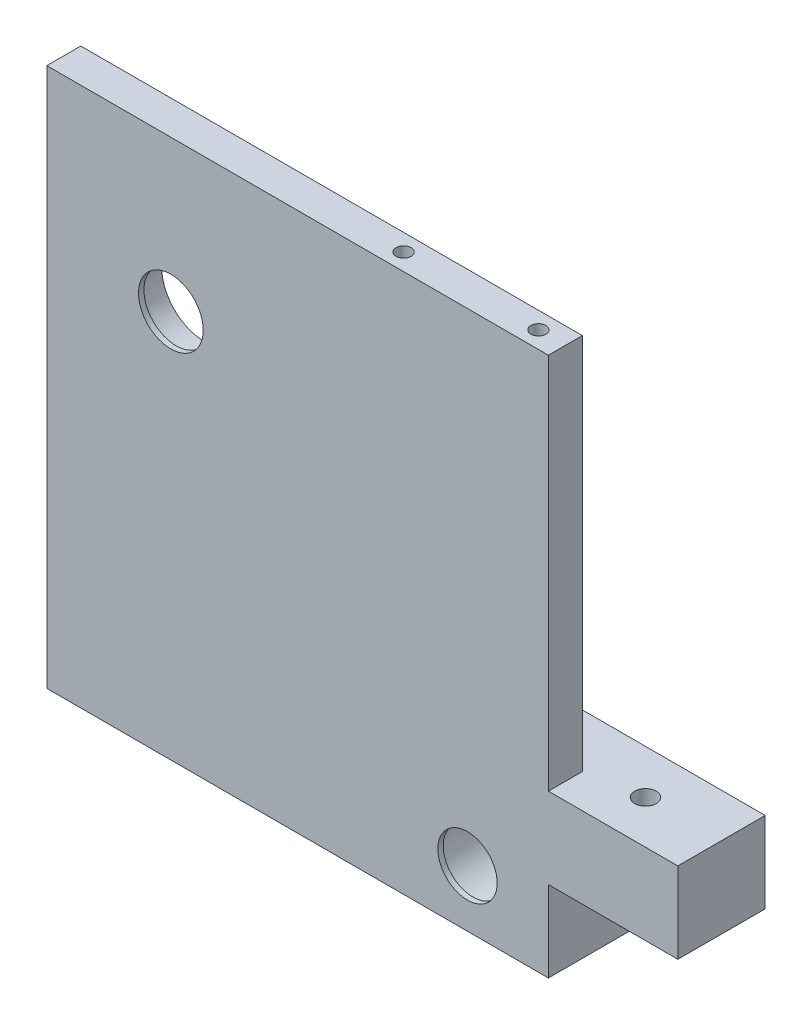
SolidWorks part; units mm, degrees
material "ABS"
ref_plane "Front Plane" through (0, 0, 0) normal (0, 0, 1) x (1, 0, 0)
ref_plane "Top Plane" through (0, 0, 0) normal (0, 1, 0) x (1, 0, 0)
ref_plane "Right Plane" through (0, 0, 0) normal (1, 0, 0) x (0, 0, -1)
sketch "Sketch1" plane through (0, 0, 0) normal (0, 0, 1) x (1, 0, 0)
  line L1 (-76.1871, 64.9281) -> (16.8129, 64.9281)
  line L2 (-76.1871, 64.9281) -> (-76.1871, -35.0719)
  line L3 (-76.1871, -35.0719) -> (16.8129, -35.0719)
  line L4 (16.8129, 64.9281) -> (16.8129, -35.0719)
  dimension "D1" = 93
  dimension "D2" = 100
extrude "Boss-Extrude2" add sketch "Sketch1" along normal blind 6.3 contours L1 L4 L3 L2
sketch "Sketch3" plane through (0, 0, 0) normal (0, 0, -1) x (-1, 0, 0)
  line L0 (76.1871, -35.0719) -> (-16.8129, -35.0719) construction
  line L1 (-16.8129, 64.9281) -> (23.1871, 64.9281)
  line L2 (-16.8129, 64.9281) -> (-16.8129, -35.0719)
  line L3 (-16.8129, -35.0719) -> (23.1871, -35.0719)
  line L4 (23.1871, 64.9281) -> (23.1871, -35.0719)
  line L5 (-16.8129, 64.9281) -> (-16.8129, -35.0719) construction
  dimension "D1" = 0
  dimension "D2" = 0
  dimension "D3" = 40
  dimension "D4" = 100
extrude "Boss-Extrude3" add sketch "Sketch3" along normal blind 9.9
sketch "Sketch4" plane through (16.8129, 0, 0) normal (1, 0, 0) x (0, 0, -1)
  line L0 (-6.3, 64.9281) -> (-6.3, -35.0719) construction
  line L1 (-6.3, -5.0719) -> (9.9, -5.0719)
  line L2 (-6.3, -5.0719) -> (-6.3, -20.0719)
  line L3 (-6.3, -20.0719) -> (9.9, -20.0719)
  line L4 (9.9, -5.0719) -> (9.9, -20.0719)
  line L5 (9.9, 64.9281) -> (9.9, -35.0719) construction
  line L6 (-6.3, -35.0719) -> (9.9, -35.0719) construction
  dimension "D1" = 15
  dimension "D2" = 15
extrude "Boss-Extrude4" add sketch "Sketch4" along normal blind 24
sketch "Sketch5" plane through (0, -5.0719, 0) normal (0, 1, 0) x (1, 0, 0)
  line L0 (40.8129, -6.3) -> (16.8129, -6.3) construction
  line L2 (16.8129, 9.9) -> (16.8129, -6.3) construction
  circle A0 centre (26.8129, 1.7) radius 2
  dimension "D2" = 4
  dimension "D3" = 10
  dimension "D1" = 8
extrude "Cut-Extrude1" cut sketch "Sketch5" against normal blind 50
sketch "Sketch6" plane through (0, 0, -9.9) normal (0, 0, -1) x (-1, 0, 0)
  line L0 (-16.8129, -35.0719) -> (23.1871, -35.0719) construction
  line L1 (-16.8129, -20.0719) -> (-16.8129, -35.0719) construction
  circle A0 centre (-1.8129, -24.5719) radius 7.5
  dimension "D1" = 15
  dimension "D2" = 10.5
  dimension "D3" = 15
extrude "Cut-Extrude2" cut sketch "Sketch6" against normal blind 50
sketch "Sketch7" plane through (0, 0, 0) normal (0, 0, -1) x (-1, 0, 0)
  line L0 (76.1871, -35.0719) -> (23.1871, -35.0719) construction
  line L2 (-16.8129, 64.9281) -> (-16.8129, -5.0719) construction
  circle A0 centre (53.1871, 36.9281) radius 8
  dimension "D1" = 16
  dimension "D2" = 72
  dimension "D3" = 70
extrude "Cut-Extrude3" cut sketch "Sketch7" against normal blind 50
extrude "Extrude-Thin1" add sketch "Sketch7<2>" along normal blind 1 from surface thin starting at face at (-45.1871, 36.9281, 6.3) thin type one direction reverse wall 2
sketch "Sketch7<2>" plane through (0, 0, 0) normal (0, 0, -1) x (-1, 0, 0) same geometry as "Sketch7"
extrude "Extrude-Thin2" add sketch "Sketch6<2>" along normal blind 1 from surface thin starting at face at (9.3129, -24.5719, 6.3) thin type one direction reverse wall 2
sketch "Sketch6<2>" plane through (0, 0, -9.9) normal (0, 0, -1) x (-1, 0, 0) same geometry as "Sketch6"
sketch "Sketch8" plane through (0, 64.9281, 0) normal (0, 1, 0) x (1, 0, 0)
  line L0 (-76.1871, -6.3) -> (16.8129, -6.3) construction
  line L1 (16.8129, 9.9) -> (-23.1871, 9.9)
  line L2 (16.8129, 9.9) -> (16.8129, -6.3)
  line L3 (16.8129, -6.3) -> (-23.1871, -6.3)
  line L4 (-23.1871, 9.9) -> (-23.1871, -6.3)
  line L5 (16.8129, 9.9) -> (-23.1871, -6.3) construction
  line L6 (16.8129, -6.3) -> (-23.1871, 9.9) construction
  line L7 (-23.1871, 9.9) -> (-23.1871, 0) construction
  circle A0 centre (9.3129, 1.8) radius 1.4
  circle A1 centre (-15.6871, 1.8) radius 1.4
  point P4 (-3.1871, 1.8)
  dimension "D1" = 25
  dimension "D2" = 7.5
  dimension "D3" = 2.8
  dimension "D4" = 2.8
  dimension "D5" = 8.1
  dimension "D6" = 8.1
extrude "Cut-Extrude4" cut sketch "Sketch8" against normal blind 20 contours A1 | A0 region at (-15.6871, 64.9281, -1.8)
sketch "Sketch9" plane through (0, 0, -9.9) normal (0, 0, -1) x (-1, 0, 0)
  line L0 (23.1871, -35.0719) -> (23.1871, 64.9281) construction
  line L1 (-16.8129, 64.9281) -> (23.1871, 64.9281)
  line L2 (-16.8129, 64.9281) -> (-16.8129, -5.0719)
  line L3 (-16.8129, -5.0719) -> (23.1871, -5.0719)
  line L4 (23.1871, 64.9281) -> (23.1871, -5.0719)
  line L5 (-16.8129, 64.9281) -> (23.1871, -5.0719) construction
  line L6 (-16.8129, -5.0719) -> (23.1871, 64.9281) construction
  line L7 (-40.8129, -5.0719) -> (-16.8129, -5.0719) construction
  point P4 (3.1871, 29.9281)
extrude "Cut-Extrude5" cut sketch "Sketch9" against normal up to surface (9.9 mm away) up to face at (-61.1871, 36.9281, 0)
sketch "Sketch10" plane through (0, 64.9281, 0) normal (0, 1, 0) x (1, 0, 0)
  line L0 (16.8129, -6.3) -> (16.8129, 0) construction
  line L1 (-76.1871, -6.3) -> (16.8129, -6.3) construction
  circle A0 centre (11.8129, -3.15) radius 1.4
  circle A1 centre (-13.1871, -3.15) radius 1.4
  dimension "D1" = 2.8
  dimension "D2" = 2.8
  dimension "D3" = 25
  dimension "D5" = 3.15
  dimension "D6" = 3.15
  dimension "D4" = 5
extrude "Cut-Extrude6" cut sketch "Sketch10" against normal blind 15
